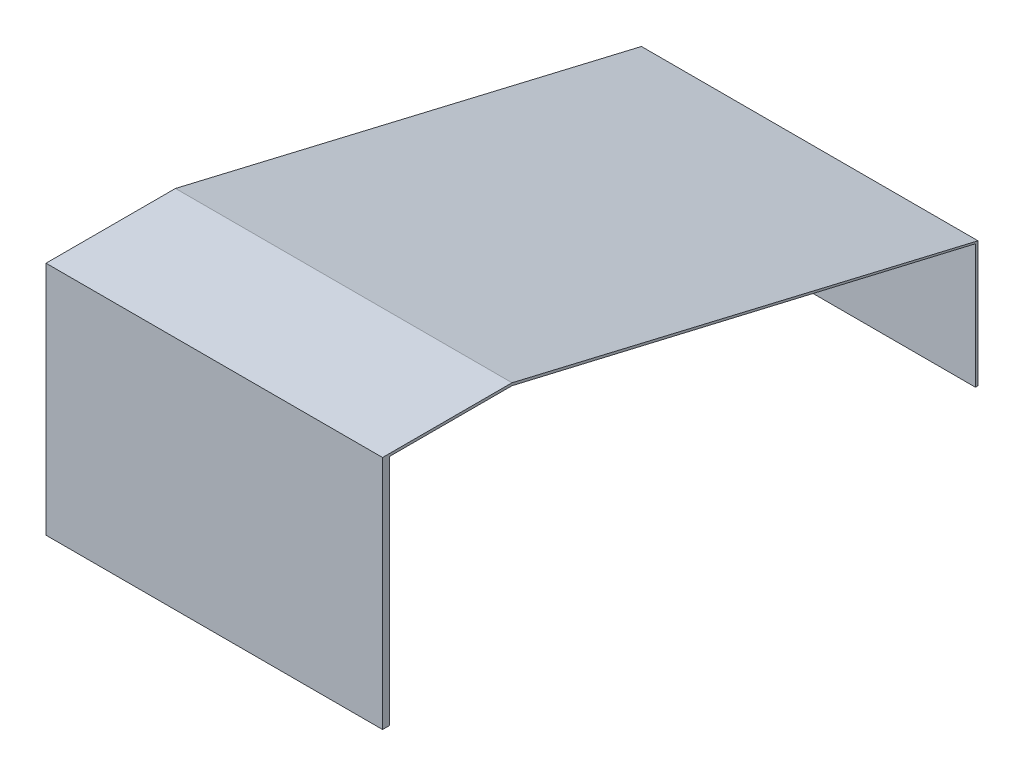
SolidWorks part; units mm, degrees
ref_plane "Alzado" through (0, 0, 0) normal (0, 0, 1) x (1, 0, 0)
ref_plane "Planta" through (0, 0, 0) normal (0, 1, 0) x (1, 0, 0)
ref_plane "Vista lateral" through (0, 0, 0) normal (1, 0, 0) x (0, 0, -1)
sketch "Sketch1" plane through (0, 0, 0) normal (0, 1, 0) x (1, 0, 0)
  line L1 (-45.9298, 50.093) -> (84.0702, 50.093)
  line L2 (-45.9298, 50.093) -> (-45.9298, -139.907)
  line L3 (-45.9298, -139.907) -> (84.0702, -139.907)
  line L4 (84.0702, 50.093) -> (84.0702, -139.907)
  dimension "D1" = 130
  dimension "D2" = 190
extrude "Boss-Extrude1" add sketch "Sketch1" along normal blind 2
sketch "Sketch2" plane through (0, 2, 0) normal (0, 1, 0) x (1, 0, 0)
  line L0 (84.0702, -139.907) -> (84.0702, 50.093) construction
  line L1 (-45.9298, -139.907) -> (84.0702, -139.907)
  line L2 (-45.9298, -139.907) -> (-45.9298, -137.2483)
  line L3 (-45.9298, -137.2483) -> (84.0702, -137.2483)
  line L4 (84.0702, -139.907) -> (84.0702, -137.2483)
extrude "Boss-Extrude2" add sketch "Sketch2" along normal blind 78
sketch "Sketch3" plane through (84.0702, 0, 0) normal (1, 0, 0) x (0, 0, -1)
  line L5 (50.093, 2) -> (90.093, 2)
  line L6 (50.093, 2) -> (50.093, 0)
  line L7 (50.093, 0) -> (90.093, 0)
  line L8 (90.093, 2) -> (90.093, 0)
  dimension "D1" = 40
extrude "Boss-Extrude3" add sketch "Sketch3" against normal blind 130
sketch "Sketch5" plane through (0, 2, 0) normal (0, 1, 0) x (1, 0, 0)
  line L0 (-45.9298, 90.093) -> (-45.9298, -137.2483) construction
  line L1 (84.0702, 90.093) -> (-45.9298, 90.093)
  line L2 (84.0702, 90.093) -> (84.0702, 89.093)
  line L3 (84.0702, 89.093) -> (-45.9298, 89.093)
  line L4 (-45.9298, 90.093) -> (-45.9298, 89.093)
  dimension "D1" = 1
extrude "Boss-Extrude4" add sketch "Sketch5" along normal blind 90
sketch "Sketch6" plane through (0, 92, 0) normal (0, 1, 0) x (1, 0, 0)
  line L1 (84.0702, 90.093) -> (-45.9298, 90.093)
  line L2 (84.0702, 90.093) -> (84.0702, -139.907)
  line L3 (84.0702, -139.907) -> (-45.9298, -139.907)
  line L4 (-45.9298, 90.093) -> (-45.9298, -139.907)
extrude "Boss-Extrude5" add sketch "Sketch6" along normal blind 1
sketch "Sketch7" plane through (0, 80, 0) normal (0, 1, 0) x (1, 0, 0)
  line L1 (-45.9298, -139.907) -> (84.0702, -139.907)
  line L2 (-45.9298, -139.907) -> (-45.9298, -137.2483)
  line L3 (-45.9298, -137.2483) -> (84.0702, -137.2483)
  line L4 (84.0702, -139.907) -> (84.0702, -137.2483)
extrude "Boss-Extrude6" add sketch "Sketch7" along normal blind 13
sketch "Sketch8" plane through (-45.9298, 0, 0) normal (-1, 0, 0) x (0, 0, 1)
  line L0 (-90.093, 0) -> (-90.093, 50) construction
  line L1 (-90.093, 0) -> (-90.093, 93) construction
  line L2 (-90.093, 93) -> (139.907, 93) construction
  line L3 (-90.093, 50) -> (89.907, 50)
  line L4 (-90.093, 50) -> (-90.093, 93)
  line L5 (-90.093, 93) -> (89.907, 93)
  line L6 (89.907, 50) -> (89.907, 93)
  dimension "D1" = 50
  dimension "D2" = 180
extrude "Boss-Extrude7" add sketch "Sketch8" against normal blind 130
chamfer "Chamfer1" distance 42.5 distance2 180 1 edges at (19.0702, 93, -90.093) first distance on face at (19.0702, 46.5, -90.093)
sketch "Sketch9" plane through (-45.9298, 0, 0) normal (-1, 0, 0) x (0, 0, 1)
  line L0 (89.907, 92) -> (-89.093, 50)
  line L1 (-89.093, 50) -> (89.907, 50)
  line L2 (89.907, 50) -> (89.907, 92)
extrude "Cut-Extrude1" cut sketch "Sketch9" against normal through all
sketch "Sketch11" plane through (0, 0, 0) normal (0, -1, 0) x (1, 0, 0)
  line L1 (-45.9298, 139.907) -> (84.0702, 139.907)
  line L2 (-45.9298, 139.907) -> (-45.9298, -90.093)
  line L3 (-45.9298, -90.093) -> (84.0702, -90.093)
  line L4 (84.0702, 139.907) -> (84.0702, -90.093)
extrude "Cut-Extrude6" cut sketch "Sketch11" against normal blind 2
